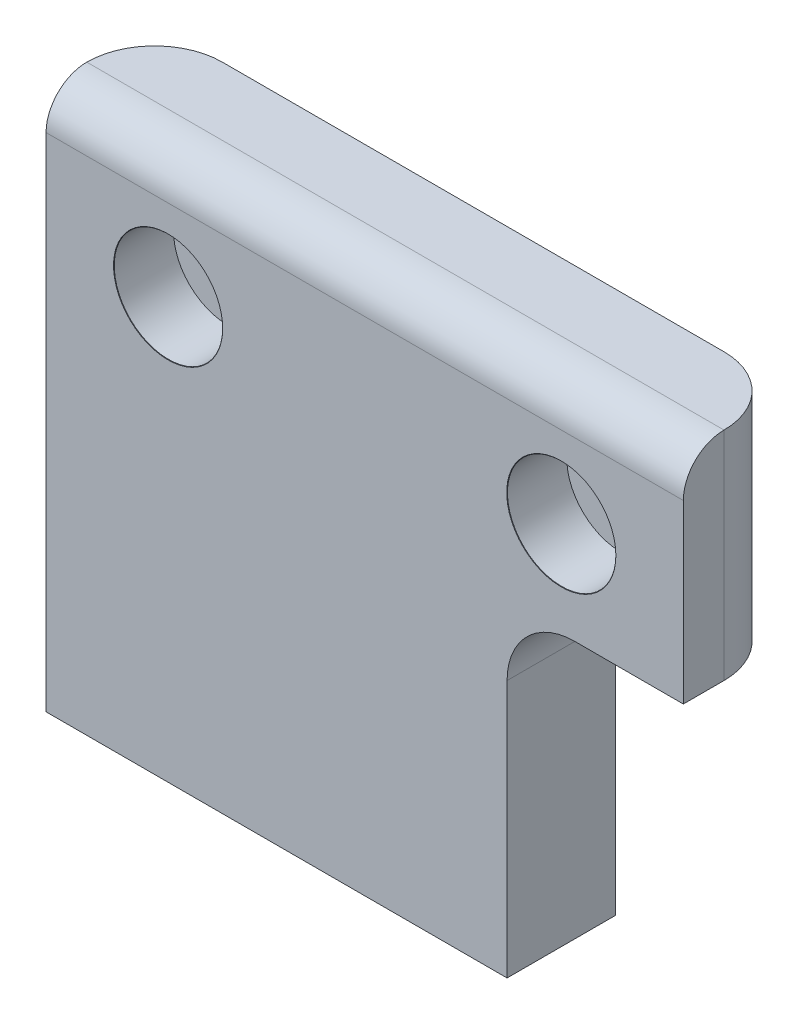
SolidWorks part; units mm, degrees
material "K110"
ref_plane "Front Plane" through (0, 0, 0) normal (0, 0, 1) x (1, 0, 0)
ref_plane "Top Plane" through (0, 0, 0) normal (0, 1, 0) x (1, 0, 0)
ref_plane "Right Plane" through (0, 0, 0) normal (1, 0, 0) x (0, 0, -1)
sketch "Sketch1" plane through (0, 0, 0) normal (0, 1, 0) x (1, 0, 0)
  line L1 (-23.5, -4) -> (23.5, -4)
  line L2 (-23.5, -4) -> (-23.5, 4)
  line L3 (-23.5, 4) -> (23.5, 4)
  line L4 (23.5, -4) -> (23.5, 4)
  line L5 (-23.5, -4) -> (23.5, 4) construction
  line L6 (-23.5, 4) -> (23.5, -4) construction
  point P0 (0, 0)
  dimension "D1" = 8
  dimension "D2" = 47
extrude "Boss-Extrude1" add sketch "Sketch1" against normal blind 40
fillet "Fillet1" radius 3 1 edges at (0, 0, 4)
fillet "Fillet2" radius 5 2 edges at (-23.5, -20, -4) (23.5, -20, -4)
hole_wizard "CBORE for M4 Hex Socket Head Cap Screw1" positions "Sketch6" profile "Sketch3" counterbore size "M4" standard "ISO" end condition through all
sketch "Sketch6" plane through (0, 0, 4) normal (0, 0, 1) x (1, 0, 0)
  line L1 (23.5, -3) -> (-23.5, -3) construction
  line L2 (-23.5, -40) -> (-23.5, -3) construction
  line L3 (23.5, -40) -> (23.5, -3) construction
  point P0 (-14.5, -9)
  point P2 (14.5, -9)
  dimension "D1" = 6
  dimension "D2" = 9
  dimension "D3" = 9
sketch "Sketch3" plane through (-14.5, -9, 4) normal (1, 0, 0) x (0, -1, 0)
  line L0 (0, 0) -> (0, 8)
  line L1 (0, 8) -> (2.15, 8)
  line L3 (2.15, 8) -> (2.15, 4.4)
  line L4 (4, 4.4) -> (2.15, 4.4)
  line L5 (4, 4.4) -> (4, 0.025)
  line L6 (4, 0.025) -> (4.025, 0)
  line L7 (4.025, 0) -> (0, 0)
  line L8 (-4, 0.025) -> (-4.025, 0) construction
  line L11 (0, -6.35) -> (0, 107.95) construction
  dimension "Thru Hole Dia." = 4.3
  dimension "Thru Hole Depth" = 8
  dimension "C'Bore Dia." = 8
  dimension "C'Bore Depth" = 4.4
  dimension "Near C'Sink Dia." = 8.05
  dimension "Near C'Sink Angle" = 90
sketch "Sketch5" plane through (0, 0, 4) normal (0, 0, 1) x (1, 0, 0)
  line L0 (23.5, -40) -> (23.5, -3) construction
  line L1 (23.5, -40) -> (10.5, -40)
  line L2 (23.5, -40) -> (23.5, -16.0022)
  line L3 (23.5, -16.0022) -> (10.5, -16.0022)
  line L4 (10.5, -40) -> (10.5, -16.0022)
  line L6 (19.4978, -28.0022) -> (29.5, -28.0022) construction
  point P5 (9, -17.5)
  point P6 (7.5, -15.004)
  point P8 (9, -17.5)
  dimension "D1" = 12
  dimension "D2" = 13
extrude "Cut-Extrude1" cut sketch "Sketch5" against normal up to next
fillet "Fillet3" radius 5 1 edges at (10.5, -16.0022, 0)
